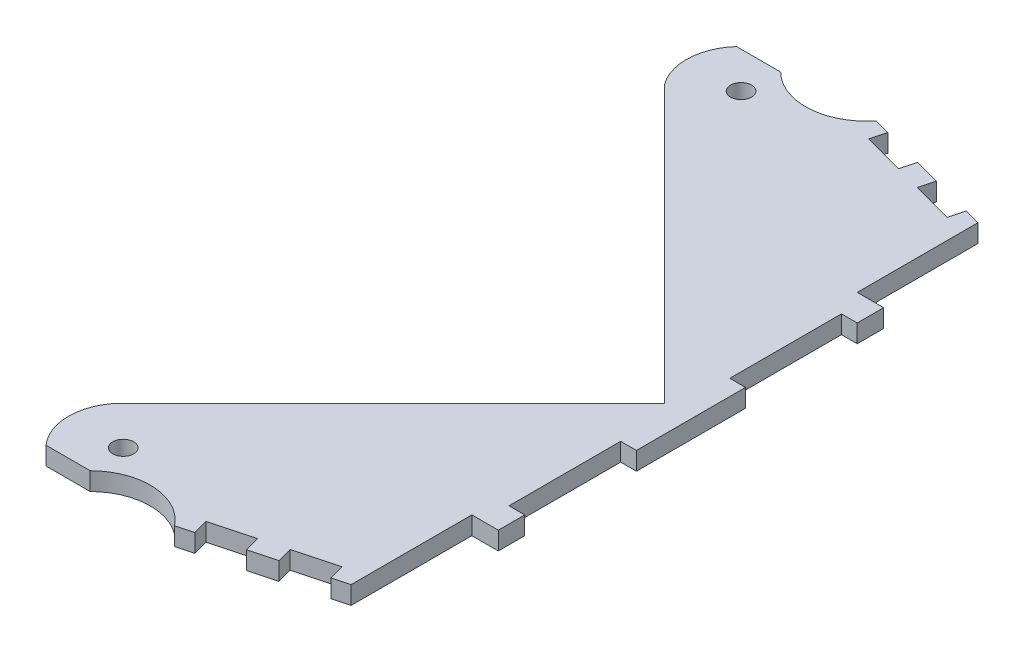
SolidWorks part; units mm, degrees
ref_plane "Front" through (0, 0, 0) normal (0, 0, 1) x (1, 0, 0)
ref_plane "Top" through (0, 0, 0) normal (0, 1, 0) x (1, 0, 0)
ref_plane "Right" through (0, 0, 0) normal (1, 0, 0) x (0, 0, -1)
ref_axis "side-side" through (80.9, 0, 0) along (-1, 0, 0)
ref_axis "up-down" through (0, 50, 0) along (0, -1, 0)
ref_axis "front-back" through (0, 0, -80.9) along (0, 0, 1)
sketch3d "3DSketch1"
  circle A2 centre (-56.825, -4.3, -104.4) radius 5
  arc A3 (-57.4357, -2.0152, -104.4) -> (-55.3111, -2.4831, -104.4) centre (-56.825, -4.3, -104.4) ccw
  circle A7 centre (-56.825, -4.3, 104.9) radius 5.5
  arc A8 (-54.8226, -3.0416, 104.4) -> (-56.6976, -1.9384, 104.4) centre (-56.825, -4.3, 104.4) ccw
  circle A9 centre (-56.825, -4.3, 104.4) radius 5
  point P7 (-56.825, -4.3, -99.4)
  point P8 (-56.825, -4.3, -102.035)
  point P19 (-56.825, -4.3, 110.4)
  point P20 (-56.825, -4.3, 102.035)
  point P22 (-56.825, -4.3, 99.4)
sketch "Sketch1" plane through (0, 0, 0) normal (0, 1, 0) x (1, 0, 0)
  line L0 (-82.6741, 104.4511) -> (-69.3102, 104.4511)
  line L1 (0, 0) -> (-83.6295, 83.6295)
  line L2 (-82.6741, -104.4511) -> (-69.3102, -104.4511)
  line L3 (0, -94.8336) -> (-42.1131, -106.1177)
  line L4 (-42.1131, 106.1177) -> (0, 94.8336)
  line L5 (-70.3102, 110) -> (-56.6019, 110) construction
  line L6 (8, 58.293) -> (8, -58.293)
  line L7 (0, 0) -> (58.8362, 0) construction
  line L8 (-69.3102, 104.4511) -> (-77.0671, 112.2079) construction
  line L10 (0, 0) -> (-83.6295, -83.6295)
  line L12 (0, -94.8336) -> (0, -58.293)
  line L13 (0, -58.293) -> (8, -58.293)
  line L16 (0, 94.8336) -> (0, 58.293)
  line L17 (0, 58.293) -> (8, 58.293)
  circle A0 centre (-70.3102, 93.4511) radius 3.175
  circle A1 centre (-70.3102, -93.4511) radius 3.175
  arc A2 (-83.6295, 83.6295) -> (-82.6741, 104.4511) centre (-70.3102, 93.4511) cw
  arc A3 (-83.6295, -83.6295) -> (-82.6741, -104.4511) centre (-70.3102, -93.4511) ccw
  circle A4 centre (-70.3102, 93.4511) radius 10.6138 construction
  arc A5 (-69.3102, 104.4511) -> (-42.1131, 106.1177) centre (-56.4487, 117.3125) ccw
  arc A6 (-69.3102, -104.4511) -> (-42.1131, -106.1177) centre (-56.4487, -117.3125) cw
  dimension "D5" = 6.35
  dimension "D1" = 21.2276
  dimension "D6" = 11
  dimension "D7" = 16.5489
  dimension "D10" = 64.6019
  dimension "D2" = 110
  dimension "D3" = 8
  dimension "D4" = 45
  dimension "D8" = 15
  dimension "D9" = 1
  dimension "D11" = 75
  dimension "D12" = 116.586
  dimension "D13" = 8
extrude "Boss-Extrude1" add sketch "Sketch1" along normal blind 5.461
chamfer "Chamfer1" [suppressed] distance 10 distance2 10
sketch "Sketch2" plane through (0, 0, 0) normal (0, 1, 0) x (1, 0, 0)
  line L4 (-17.1928, -99.4404) -> (-4.8296, -96.1276)
  line L5 (-4.8296, -96.1276) -> (-6.0623, -91.5274)
  line L6 (-6.0623, -91.5274) -> (-18.4255, -94.8401)
  line L7 (-18.4255, -94.8401) -> (-17.1928, -99.4404)
  line L8 (-17.1928, -99.4404) -> (-4.8296, -96.1276)
  line L9 (-4.8296, -96.1276) -> (-6.0623, -91.5274)
  line L10 (-6.0623, -91.5274) -> (-18.4255, -94.8401)
  line L11 (-18.4255, -94.8401) -> (-17.1928, -99.4404)
  line L12 (-37.2834, -104.8236) -> (-24.9202, -101.5109)
  line L13 (-24.9202, -101.5109) -> (-26.1529, -96.9107)
  line L14 (-26.1529, -96.9107) -> (-38.5161, -100.2234)
  line L15 (-38.5161, -100.2234) -> (-37.2834, -104.8236)
  line L16 (-37.2834, -104.8236) -> (-24.9202, -101.5109)
  line L17 (-24.9202, -101.5109) -> (-26.1529, -96.9107)
  line L18 (-26.1529, -96.9107) -> (-38.5161, -100.2234)
  line L19 (-38.5161, -100.2234) -> (-37.2834, -104.8236)
  line L20 (3.2375, -50.293) -> (8, -50.293)
  line L21 (8, -50.293) -> (8, -16.51)
  line L22 (8, -16.51) -> (3.2375, -16.51)
  line L23 (3.2375, -16.51) -> (3.2375, -50.293)
  line L24 (3.2375, -50.293) -> (8, -50.293)
  line L25 (8, -50.293) -> (8, -16.51)
  line L26 (8, -16.51) -> (3.2375, -16.51)
  line L27 (3.2375, -16.51) -> (3.2375, -50.293)
  line L28 (-38.5161, 100.2234) -> (-26.1529, 96.9107)
  line L29 (-26.1529, 96.9107) -> (-24.9202, 101.5109)
  line L30 (-24.9202, 101.5109) -> (-37.2834, 104.8236)
  line L31 (-37.2834, 104.8236) -> (-38.5161, 100.2234)
  line L32 (-38.5161, 100.2234) -> (-26.1529, 96.9107)
  line L33 (-26.1529, 96.9107) -> (-24.9202, 101.5109)
  line L34 (-24.9202, 101.5109) -> (-37.2834, 104.8236)
  line L35 (-37.2834, 104.8236) -> (-38.5161, 100.2234)
  line L36 (-18.4255, 94.8401) -> (-6.0623, 91.5274)
  line L37 (-6.0623, 91.5274) -> (-4.8296, 96.1276)
  line L38 (-4.8296, 96.1276) -> (-17.1928, 99.4404)
  line L39 (-17.1928, 99.4404) -> (-18.4255, 94.8401)
  line L40 (-18.4255, 94.8401) -> (-6.0623, 91.5274)
  line L41 (-6.0623, 91.5274) -> (-4.8296, 96.1276)
  line L42 (-4.8296, 96.1276) -> (-17.1928, 99.4404)
  line L43 (-17.1928, 99.4404) -> (-18.4255, 94.8401)
  line L44 (3.2375, 50.293) -> (3.2375, 16.51)
  line L45 (3.2375, 16.51) -> (8, 16.51)
  line L46 (8, 16.51) -> (8, 50.293)
  line L47 (8, 50.293) -> (3.2375, 50.293)
  line L48 (3.2375, 50.293) -> (3.2375, 16.51)
  line L49 (3.2375, 16.51) -> (8, 16.51)
  line L50 (8, 16.51) -> (8, 50.293)
  line L51 (8, 50.293) -> (3.2375, 50.293)
  dimension "D1" = 0
  dimension "D2" = 0
  dimension "D3" = 0
  dimension "D4" = 0
  dimension "D5" = 0
  dimension "D6" = 0
extrude "Cut-Extrude1" cut sketch "Sketch2" along normal through all
